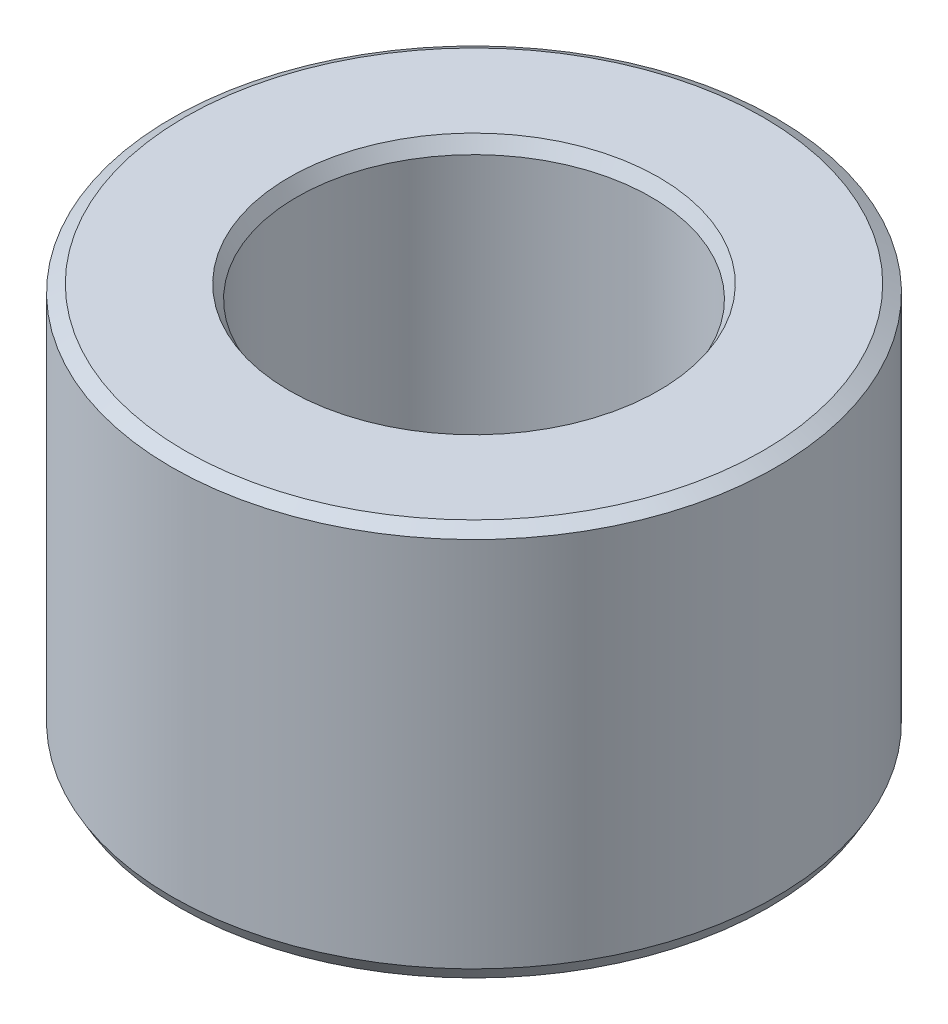
SolidWorks part; units mm, degrees
ref_plane "Front Plane" through (0, 0, 0) normal (0, 0, 1) x (1, 0, 0)
ref_plane "Top Plane" through (0, 0, 0) normal (0, 1, 0) x (1, 0, 0)
ref_plane "Right Plane" through (0, 0, 0) normal (1, 0, 0) x (0, 0, -1)
sketch "Sketch1" plane through (0, 0, 0) normal (0, 1, 0) x (1, 0, 0)
  circle A0 centre (0, 0) radius 35
  dimension "SLEEVE_OD" = 70
extrude "Boss-Extrude1" add sketch "Sketch1" along normal blind 45.476
sketch "Sketch2" plane through (0, 0, 0) normal (0, 1, 0) x (1, 0, 0)
  circle A0 centre (0, 0) radius 20.5089
  dimension "BORE_D" = 41.0179
extrude "Cut-Extrude1" cut sketch "Sketch2" along normal through all
chamfer "Chamfer1" distance 0.8867 angle 60 4 edges at (0, 45.476, 20.5089) (0, 0, 20.5089) (0, 0, 35) (0, 45.476, 35) first distance on face at (0, 45.476, 20.5089) first distance on face at (0, 0, 20.5089) first distance on face at (0, 45.476, 35)
